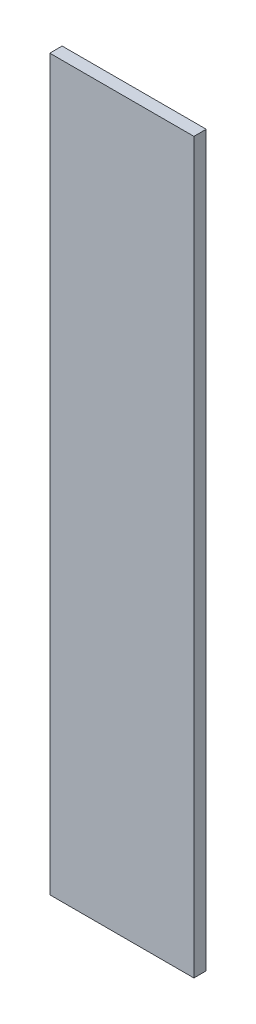
SolidWorks part; units mm, degrees
ref_plane "Front Plane" through (0, 0, 0) normal (0, 0, 1) x (1, 0, 0)
ref_plane "Top Plane" through (0, 0, 0) normal (0, 1, 0) x (1, 0, 0)
ref_plane "Right Plane" through (0, 0, 0) normal (1, 0, 0) x (0, 0, -1)
sketch "Sketch1" plane through (0, 0, 0) normal (0, 0, 1) x (1, 0, 0)
  line L1 (-17.5, -88.5) -> (17.5, -88.5)
  line L2 (-17.5, -88.5) -> (-17.5, 88.5)
  line L3 (-17.5, 88.5) -> (17.5, 88.5)
  line L4 (17.5, -88.5) -> (17.5, 88.5)
  line L5 (-17.5, -88.5) -> (17.5, 88.5) construction
  line L6 (-17.5, 88.5) -> (17.5, -88.5) construction
  point P0 (0, 0)
  dimension "D1" = 177
  dimension "D2" = 35
extrude "Boss-Extrude1" add sketch "Sketch1" along normal blind 3
equation "\"PCLength\"= 320mm'Length across I/O from PS to GPU"
equation "\"PCWidth\"= 242mm'Distance of longest part parallel to GPU(ussually GPU)"
equation "\"PCHeight\"= 172mm'Tallest point with mobo laying flat"
equation "\"WallThickness\"= 9mm'Thickness of each outer tank wall"
equation "\"ThermoBarrierThickness\"= 3mm'Thickness of barrier between hot side and cold side"
equation "\"HotSideGap\"= 35mm'Space in the hot side for a pump"
equation "\"PCClearance\"= 30mm'Clearance from top of tank to top of PC"
equation "\"RadiatorHeight\"= 275mm'Final Height from ground of radiators"
equation "\"D1@Distance1\"=\"HotSideGap\""
equation "\"AirflowGap\"= 36mm'Distance between radiators and tank for airflow"
equation "\"D1@Sketch1\"=\"PCHeight\" + 5"
equation "\"D2@Sketch1\"=\"HotSideGap\""
equation "\"D1@Boss-Extrude1\"=\"ThermoBarrierThickness\""
